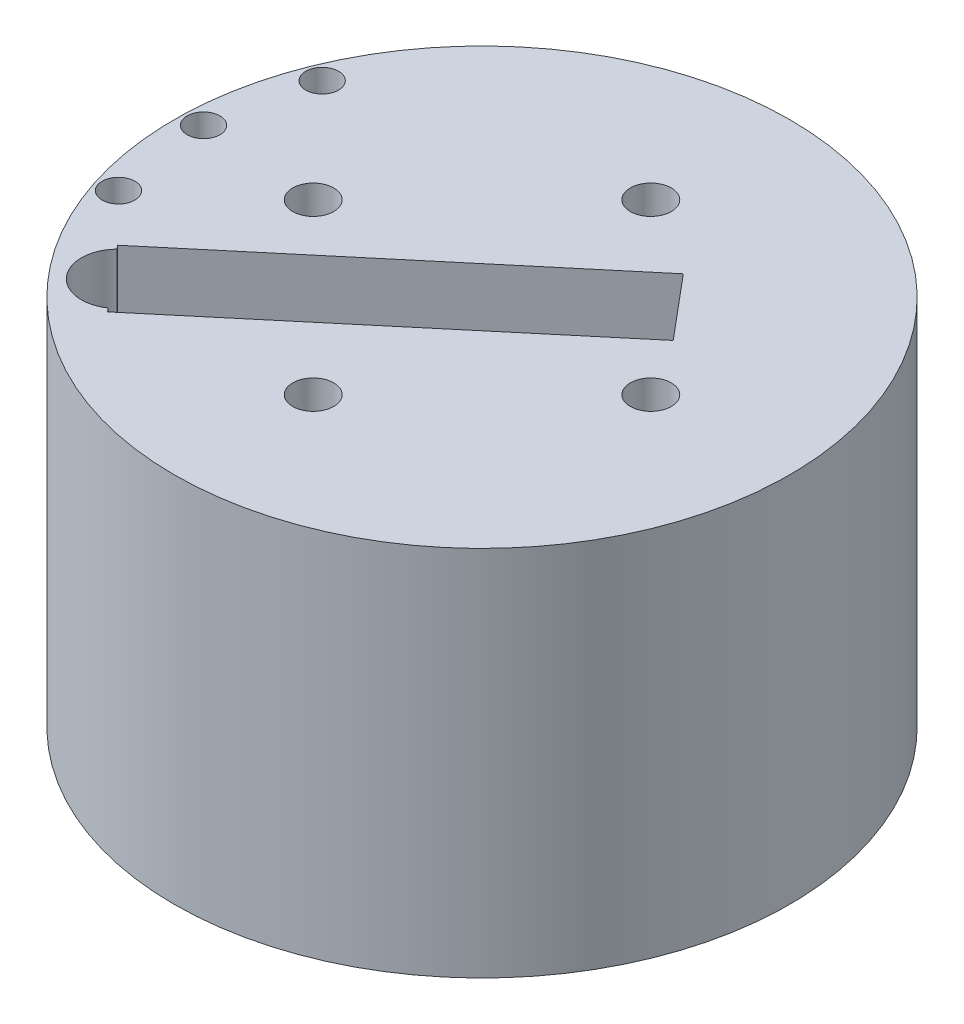
SolidWorks part; units mm, degrees
ref_plane "Front Plane" through (0, 0, 0) normal (0, 0, 1) x (1, 0, 0)
ref_plane "Top Plane" through (0, 0, 0) normal (0, 1, 0) x (1, 0, 0)
ref_plane "Right Plane" through (0, 0, 0) normal (1, 0, 0) x (0, 0, -1)
sketch "Sketch2" plane through (0, 0, 0) normal (0, 1, 0) x (1, 0, 0)
  circle A0 centre (0, 0) radius 47.6885
  dimension "D1" = 95.377
extrude "Boss-Extrude1" add sketch "Sketch2" along normal blind 57.658
sketch "Sketch4" plane through (0, 57.658, 0) normal (0, 1, 0) x (1, 0, 0)
  circle A1 centre (-26.162, 0) radius 3.175
  circle A2 centre (26.162, 0) radius 3.175
  circle A3 centre (0, 26.162) radius 3.175
  circle A4 centre (0, -26.162) radius 3.175
sketch "Sketch5" plane through (0, 57.658, 0) normal (0, 1, 0) x (1, 0, 0)
  line L0 (0, 0) -> (-44.6487, 1.4926)
  line L1 (0, 0) -> (-41.4455, 16.6734)
  line L2 (0, 0) -> (-42.4665, -13.8681)
  line L4 (0, 0) -> (-30.6943, -25.7555)
  circle A1 centre (-41.4455, 16.6734) radius 2.54
  circle A2 centre (0, 0) radius 44.6736
  circle A3 centre (-44.6487, 1.4926) radius 2.54
  circle A4 centre (-42.4665, -13.8681) radius 2.54
  circle A9 centre (-30.6943, -25.7555) radius 5.6388
  dimension "D3" = 11.2776
  dimension "D5" = 89.3472
  dimension "D1" = 20
  dimension "D2" = 20
  dimension "D6" = 21.915
  dimension "D4" = 40.0685
extrude "Cut-Extrude2" cut sketch "Sketch5" against normal through all contours A9 | A1 | A3 | A4
extrude "Cut-Extrude3" cut sketch "Sketch4" against normal through all
sketch "Sketch6" plane through (0, 57.658, 0) normal (0, 1, 0) x (1, 0, 0)
  line L1 (-27.0503, -30.9873) -> (20.6206, 9.0134)
  line L2 (-27.0503, -30.9873) -> (-35.2137, -21.2585)
  line L3 (-35.2137, -21.2585) -> (12.4572, 18.7422)
  line L4 (20.6206, 9.0134) -> (12.4572, 18.7422)
  dimension "D1" = 62.23
  dimension "D2" = 12.7
  dimension "D3" = 6.35
  dimension "D4" = 21.59
  dimension "D5" = 90
  dimension "D6" = 90
  dimension "D7" = 90
extrude "Cut-Extrude4" cut sketch "Sketch6" against normal blind 43.18
sketch "Sketch11" plane through (0, 0, 0) normal (0, -1, 0) x (1, 0, 0)
  circle A0 centre (0, 26.162) radius 6.35
  circle A1 centre (26.162, 0) radius 6.35
  circle A2 centre (0, -26.162) radius 6.35
  circle A3 centre (-26.162, 0) radius 6.35
  dimension "D1" = 12.7
  dimension "D2" = 12.7
  dimension "D3" = 12.7
  dimension "D4" = 12.7
extrude "Cut-Extrude7" cut sketch "Sketch11" against normal blind 7.62
sketch "Sketch14" plane through (0, 0, 0) normal (0, -1, 0) x (1, 0, 0)
  circle A0 centre (1.3569, -14.949) radius 2.067
  circle A1 centre (4.5237, 8.9723) radius 2.067
extrude "Cut-Extrude8" cut sketch "Sketch14" against normal blind 19.05
equation "\"D4@Sketch5\"=(3.755/2)-(0.5/2)-0.05"
equation "\"D1@Sketch6\"=2.10 + (0.85-0.5)"
